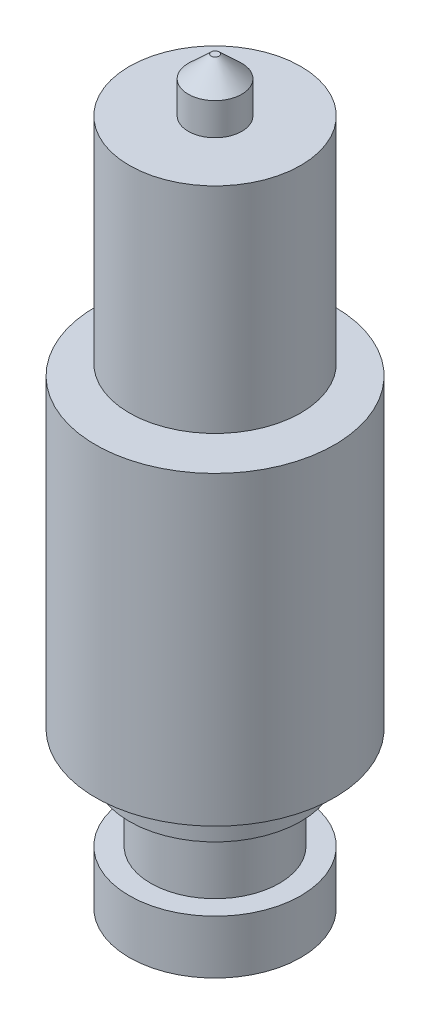
SolidWorks part; units mm, degrees
material "AISI 1035 Steel (SS)"
ref_plane "Front Plane" through (0, 0, 0) normal (0, 0, 1) x (1, 0, 0)
ref_plane "Top Plane" through (0, 0, 0) normal (0, 1, 0) x (1, 0, 0)
ref_plane "Right Plane" through (0, 0, 0) normal (1, 0, 0) x (0, 0, -1)
sketch "Sketch1" plane through (0, 0, 0) normal (0, 1, 0) x (1, 0, 0)
  circle A0 centre (0, 0) radius 8
  dimension "D1" = 16
extrude "Boss-Extrude1" add sketch "Sketch1" along normal blind 5
sketch "Sketch2" plane through (0, 5, 0) normal (0, 1, 0) x (1, 0, 0)
  circle A0 centre (0, 0) radius 6
  dimension "D1" = 12
extrude "Boss-Extrude2" add sketch "Sketch2" along normal blind 6
sketch "Sketch3" plane through (0, 11, 0) normal (0, 1, 0) x (1, 0, 0)
  circle A0 centre (0, 0) radius 8
  dimension "D1" = 16
extrude "Boss-Extrude3" add sketch "Sketch3" along normal blind 1.5
sketch "Sketch4" plane through (0, 12.5, 0) normal (0, 1, 0) x (1, 0, 0)
  circle A0 centre (0, 0) radius 5
  dimension "D1" = 10
extrude "Boss-Extrude4" add sketch "Sketch4" along normal blind 2
sketch "Sketch5" plane through (0, 14.5, 0) normal (0, 1, 0) x (1, 0, 0)
  circle A0 centre (0, 0) radius 11.15
  dimension "D1" = 22.3
extrude "Boss-Extrude5" add sketch "Sketch5" along normal blind 28.5
sketch "Sketch6" plane through (0, 43, 0) normal (0, 1, 0) x (1, 0, 0)
  circle A0 centre (0, 0) radius 2
  dimension "D1" = 4
extrude "Boss-Extrude6" add sketch "Sketch6" along normal blind 1
sketch "Sketch7" plane through (0, 44, 0) normal (0, 1, 0) x (1, 0, 0)
  circle A0 centre (0, 0) radius 8
  dimension "D1" = 16
extrude "Boss-Extrude7" add sketch "Sketch7" along normal blind 20
sketch "Sketch8" plane through (0, 64, 0) normal (0, 1, 0) x (1, 0, 0)
  circle A0 centre (0, 0) radius 2.5
  dimension "D1" = 5
extrude "Boss-Extrude8" add sketch "Sketch8" along normal blind 3
sketch "Sketch9" plane through (0, 67, 0) normal (0, 1, 0) x (1, 0, 0)
  circle A0 centre (0, 0) radius 2.5
extrude "Boss-Extrude9" add sketch "Sketch9" along normal blind 2 draft 47
ref_plane "Plane1" through (0, 0, 0) normal (0, 0, 1) x (1, 0, 0)
sketch "草图1" plane through (0, 0, 0) normal (0, -1, 0) x (-1, 0, 0)
  circle A0 centre (0, 0) radius 1
  dimension "D1" = 2
extrude "切除-拉伸1" cut sketch "草图1" against normal blind 10
equation "\"D1@Boss-Extrude5\"=43-12.5-2"
